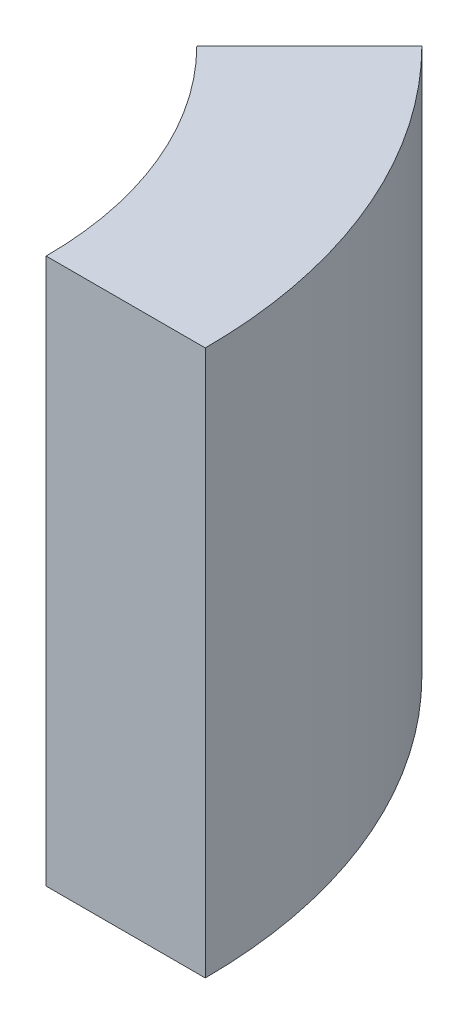
SolidWorks part; units mm, degrees
ref_plane "Front Plane" through (0, 0, 0) normal (0, 0, 1) x (1, 0, 0)
ref_plane "Top Plane" through (0, 0, 0) normal (0, 1, 0) x (1, 0, 0)
ref_plane "Right Plane" through (0, 0, 0) normal (1, 0, 0) x (0, 0, -1)
sketch "Sketch1" plane through (0, 0, 0) normal (0, 1, 0) x (1, 0, 0)
  line L0 (0, 0) -> (39.7333, 0) construction
  line L1 (11.3137, 11.3137) -> (16.2635, 16.2635)
  line L2 (16, 0) -> (23, 0)
  line L3 (14.7821, 6.1229) -> (0, 0) construction
  arc A0 (16, 0) -> (11.3137, 11.3137) centre (0, 0) ccw
  arc A1 (23, 0) -> (16.2635, 16.2635) centre (0, 0) ccw
  point P6 (14.7821, 6.1229)
  dimension "D1" = 16
  dimension "D3" = 23
  dimension "D4" = 7
  dimension "D2" = 45
  dimension "D5" = 22.5
extrude "Boss-Extrude1" add sketch "Sketch1" along normal blind 24
fillet "Fillet1" [suppressed] radius 0.4
sketch "Sketch2" plane through (0, 0, 0) normal (-0.7071, 0, -0.7071) x (-0.7071, 0, 0.7071)
  line L0 (-19.7, 5.2732) -> (-19.7, 21.6424) construction
  line L1 (-23, 24) -> (-23, 0) construction
  point P4 (0, 0)
  dimension "D1" = 3.3
sketch "Sketch3" plane through (0, 0, 0) normal (0, 0, 1) x (1, 0, 0)
  line L0 (19.7, 25.7921) -> (19.7, 3.555) construction
  line L1 (23, 24) -> (23, 0) construction
  dimension "D1" = 3.3
sketch "Sketch4" plane through (0, 0, 0) normal (0, -1, 0) x (1, 0, 0)
  line L0 (14.4414, -6.8882) -> (18.9543, -9.0407)
  line L1 (19.7955, -7.0099) -> (15.0823, -5.3409)
  line L2 (14.7821, -6.1229) -> (21.2492, -8.8017) construction
  arc A0 (11.3137, -11.3137) -> (16, 0) centre (0, 0) ccw construction
  arc A1 (18.9543, -9.0407) -> (19.7955, -7.0099) centre (0, 0) ccw
  arc A2 (16.2635, -16.2635) -> (23, 0) centre (0, 0) ccw construction
  arc A3 (15.0823, -5.3409) -> (14.4414, -6.8882) centre (0, 0) cw
  point P12 (19.4015, -8.0364)
  dimension "D1" = 2
  dimension "D2" = 6
extrude "Boss-Extrude2" add sketch "Sketch4" along normal blind 1.5
